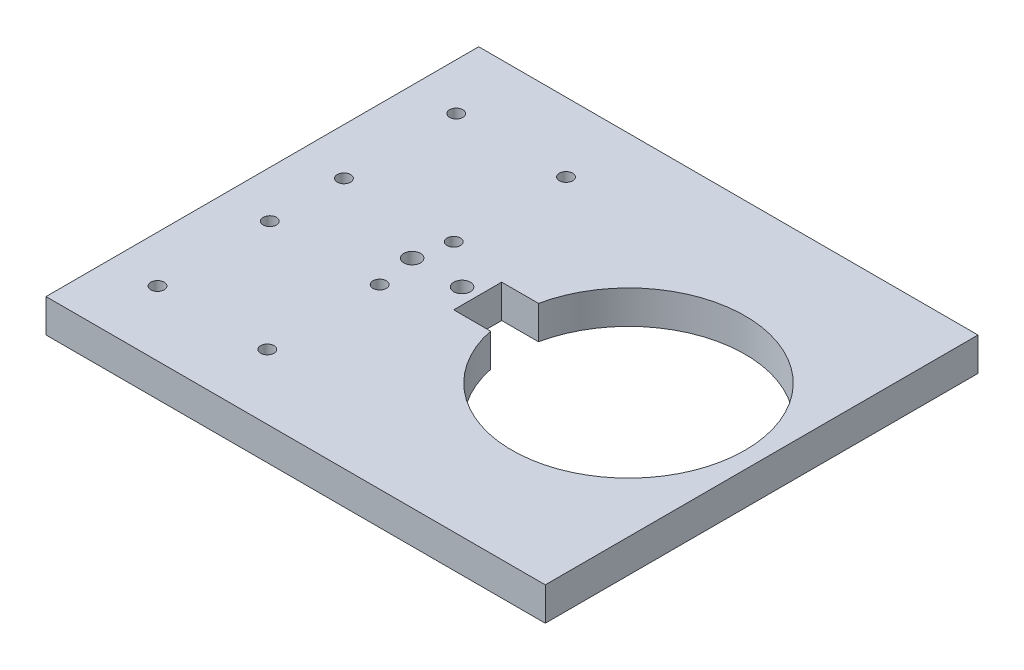
SolidWorks part; units mm, degrees
ref_plane "Front Plane" through (0, 0, 0) normal (0, 0, 1) x (1, 0, 0)
ref_plane "Top Plane" through (0, 0, 0) normal (0, 1, 0) x (1, 0, 0)
ref_plane "Right Plane" through (0, 0, 0) normal (1, 0, 0) x (0, 0, -1)
sketch "Sketch1" plane through (0, 0, 0) normal (0, 1, 0) x (1, 0, 0)
  line L0 (0.7506, -7.2095) -> (-10.3057, -7.2095)
  line L1 (-75, -65) -> (75, -65)
  line L2 (-75, -65) -> (-75, 65)
  line L3 (-75, 65) -> (75, 65)
  line L4 (75, -65) -> (75, 65)
  line L5 (-75, -65) -> (-8.3186, -7.2095) construction
  line L6 (-75, 65) -> (-8.3186, 7.2095) construction
  line L10 (-10.3057, -7.2095) -> (-10.3057, 7.2095)
  line L15 (0.7506, 7.2095) -> (-10.3057, 7.2095)
  line L16 (39.9746, 34.6447) -> (75, 65) construction
  line L17 (39.9746, -34.6447) -> (75, -65) construction
  arc A0 (0.7506, -7.2095) -> (0.7506, 7.2095) centre (35, 0) ccw
  circle A1 centre (-15, 0) radius 2.5
  circle A2 centre (-30, 0) radius 2.5
  circle A3 centre (-61, -11.7622) radius 2
  circle A4 centre (-61, -45.5) radius 2
  circle A5 centre (-28, -45.5) radius 2
  circle A6 centre (-28, -11.7622) radius 2
  circle A7 centre (-28, 10.5) radius 2
  circle A8 centre (-61, 10.5) radius 2
  circle A9 centre (-61, 44.2378) radius 2
  circle A10 centre (-28, 44.2378) radius 2
  point P0 (0, 0)
  point P8 (0, 0)
  dimension "D3" = 70
  dimension "D1" = 130
  dimension "D2" = 150
  dimension "D4" = 40
  dimension "D5" = 0
extrude "Boss-Extrude1" add sketch "Sketch1" along normal blind 10
